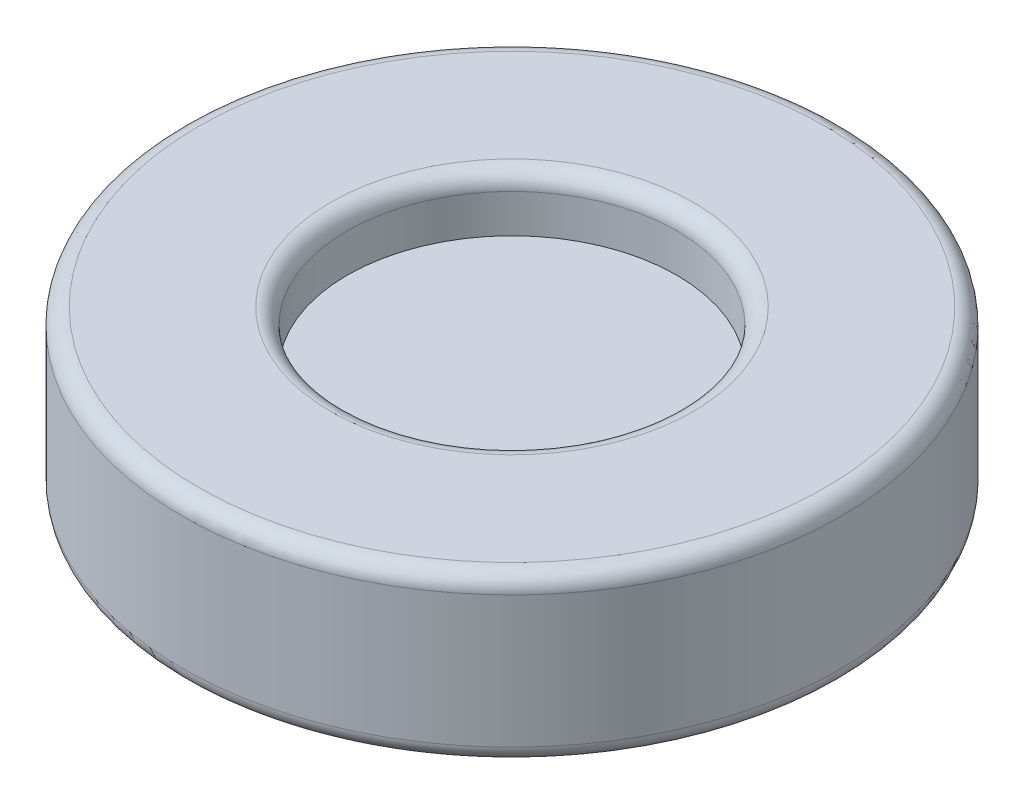
SolidWorks part; units mm, degrees
ref_plane "Front Plane" through (0, 0, 0) normal (0, 0, 1) x (1, 0, 0)
ref_plane "Top Plane" through (0, 0, 0) normal (0, 1, 0) x (1, 0, 0)
ref_plane "Right Plane" through (0, 0, 0) normal (1, 0, 0) x (0, 0, -1)
sketch "Sketch1" plane through (0, 0, 0) normal (0, 0, 1) x (1, 0, 0)
  line L0 (-32.7969, 0) -> (-57.15, 0) construction
  line L5 (0, 6.35) -> (0, -6.35)
  line L6 (0, 6.35) -> (-38.1, 6.35)
  line L7 (55, 0) -> (-55, 0) construction
  line L8 (0, -6.35) -> (-38.1, -6.35)
  line L9 (-38.1, -19.05) -> (-76.2, -19.05)
  line L10 (-38.1, -19.05) -> (-38.1, -6.35)
  line L11 (-38.1, 19.05) -> (-76.2, 19.05)
  line L12 (-76.2, -19.05) -> (-76.2, 19.05)
  line L13 (-38.1, -19.05) -> (-76.2, 19.05) construction
  line L14 (-38.1, 19.05) -> (-76.2, -19.05) construction
  line L15 (-38.1, 6.35) -> (-38.1, 19.05)
  point P0 (0, 0)
  point P1 (0, 0)
  point P4 (0, 0)
  dimension "D1" = 38.1
  dimension "D2" = 38.1
  dimension "D3" = 12.7
  dimension "D4" = 38.1
  dimension "D5" = 12.7
revolve "Revolve1" add sketch "Sketch1" angle 360 about L5
fillet "Fillet2" radius 3.81 4 edges at (-76.2, -19.05, 0) (-76.2, 19.05, 0) (-38.1, -19.05, 0) (-38.1, 19.05, 0)
